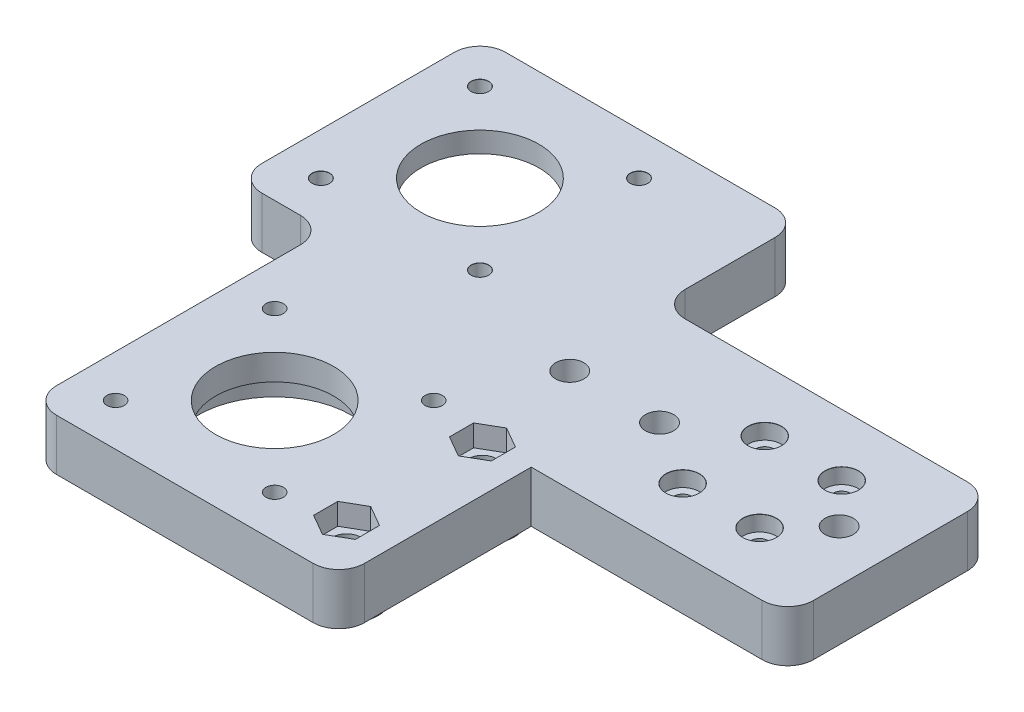
SolidWorks part; units mm, degrees
ref_plane "Front Plane" through (0, 0, 0) normal (0, 0, 1) x (1, 0, 0)
ref_plane "Top Plane" through (0, 0, 0) normal (0, 1, 0) x (1, 0, 0)
ref_plane "Right Plane" through (0, 0, 0) normal (1, 0, 0) x (0, 0, -1)
sketch "Sketch1" plane through (0, 0, 0) normal (0, 1, 0) x (1, 0, 0)
  line L0 (0, 0) -> (110, 0) construction
  line L1 (110, 0) -> (110, 20) construction
  line L2 (110, 20) -> (0, 20) construction
  line L3 (0, 20) -> (0, 0) construction
  line L4 (110, 30) -> (110, -10) construction
  line L5 (110, 30) -> (80, 30) construction
  line L6 (80, 30) -> (80, -10) construction
  line L7 (80, -10) -> (110, -10) construction
  line L8 (0, 67.5) -> (0, -47.5)
  line L16 (0, 67.5) -> (60, 67.5)
  line L18 (0, -47.5) -> (60, -47.5)
  line L19 (60, 67.5) -> (60, 30)
  line L22 (110, -10) -> (60, -10)
  line L23 (60, -10) -> (60, -47.5)
  line L24 (60, 30) -> (110, 30)
  line L25 (110, 30) -> (110, -10)
  point P8 (110, 10)
  point P13 (0, 10)
  dimension "D1" = 20
  dimension "D2" = 37.5
  dimension "D3" = 30
  dimension "D4" = 40
  dimension "D5" = 110
  dimension "D6" = 20
extrude "Boss-Extrude1" add sketch "Sketch1" along normal blind 10
fillet "Fillet1" radius 5 7 edges at (60, 5, -30) (110, 5, -30) (110, 5, 10) (0, 5, 47.5) (0, 5, -67.5) (60, 5, -67.5) (60, 5, 47.5)
sketch "Sketch3" plane through (0, 10, 0) normal (0, 1, 0) x (1, 0, 0)
  line L0 (5, -47.5) -> (55, -47.5) construction
  line L1 (0, 62.5) -> (0, -42.5) construction
  circle A0 centre (23.75, -23.75) radius 11.5
  dimension "D3" = 23
  dimension "D1" = 23.75
  dimension "D2" = 23.75
extrude "Cut-Extrude1" cut sketch "Sketch3" against normal blind 10
sketch "Sketch4" plane through (0, 0, 0) normal (0, -1, 0) x (1, 0, 0)
  line L1 (39.25, 39.25) -> (8.25, 39.25)
  line L2 (39.25, 39.25) -> (39.25, 8.25)
  line L3 (39.25, 8.25) -> (8.25, 8.25)
  line L4 (8.25, 39.25) -> (8.25, 8.25)
  line L5 (39.25, 39.25) -> (8.25, 8.25) construction
  line L6 (39.25, 8.25) -> (8.25, 39.25) construction
  point P0 (23.75, 23.75)
  dimension "D1" = 31
hole_wizard "CBORE for M3 SHCS1" positions "Sketch5" profile "Sketch6" counterbore size "M3" standard "ANSI Metric" end condition through all
sketch "Sketch5" plane through (0, 0, 0) normal (0, -1, 0) x (-1, 0, 0)
  point P0 (-39.25, -8.25)
  point P3 (-8.25, -39.25)
  point P6 (-8.25, -8.25)
  point P9 (-39.25, -39.25)
sketch "Sketch6" plane through (39.25, 0, 8.25) normal (1, 0, 0) x (0, 0, -1)
  line L0 (0, 0) -> (0, 10)
  line L1 (0, 10) -> (1.7, 10)
  line L3 (1.7, 10) -> (1.7, 3)
  line L4 (3.25, 3) -> (1.7, 3)
  line L5 (3.25, 3) -> (3.25, 0.025)
  line L6 (3.25, 0.025) -> (3.275, 0)
  line L7 (3.275, 0) -> (0, 0)
  line L8 (-3.25, 0.025) -> (-3.275, 0) construction
  line L11 (0, -6.35) -> (0, 107.95) construction
  dimension "Thru Hole Dia." = 3.4
  dimension "Thru Hole Depth" = 10
  dimension "C'Bore Dia." = 6.5
  dimension "C'Bore Depth" = 3
  dimension "Near C'Sink Dia." = 6.55
  dimension "Near C'Sink Angle" = 90
sketch "Sketch7" plane through (0, 10, 0) normal (0, 1, 0) x (1, 0, 0)
  line L1 (92.5, 18) -> (77.5, 18)
  line L2 (92.5, 18) -> (92.5, 2)
  line L3 (92.5, 2) -> (77.5, 2)
  line L4 (77.5, 18) -> (77.5, 2)
  line L5 (92.5, 18) -> (77.5, 2) construction
  line L6 (92.5, 2) -> (77.5, 18) construction
  line L7 (110, 10) -> (0, 10)
  line L8 (0, 67.5) -> (0, -47.5) construction
  line L10 (110, 30) -> (110, -10) construction
  point P0 (85, 10)
  dimension "D1" = 15
  dimension "D2" = 16
  dimension "D3" = 25
hole_wizard "CBORE for M3 SHCS2" positions "Sketch8" profile "Sketch9" counterbore size "M3" standard "ANSI Metric" end condition through all
sketch "Sketch8" plane through (0, 10, 0) normal (0, 1, 0) x (1, 0, 0)
  point P0 (77.5, 18)
  point P3 (92.5, 18)
  point P6 (92.5, 2)
  point P9 (77.5, 2)
sketch "Sketch9" plane through (77.5, 10, -18) normal (1, 0, 0) x (0, 0, 1)
  line L0 (0, 0) -> (0, 10)
  line L1 (0, 10) -> (1.7, 10)
  line L3 (1.7, 10) -> (1.7, 3)
  line L4 (3.25, 3) -> (1.7, 3)
  line L5 (3.25, 3) -> (3.25, 0.025)
  line L6 (3.25, 0.025) -> (3.275, 0)
  line L7 (3.275, 0) -> (0, 0)
  line L8 (-3.25, 0.025) -> (-3.275, 0) construction
  line L11 (0, -6.35) -> (0, 107.95) construction
  dimension "Thru Hole Dia." = 3.4
  dimension "Thru Hole Depth" = 10
  dimension "C'Bore Dia." = 6.5
  dimension "C'Bore Depth" = 3
  dimension "Near C'Sink Dia." = 6.55
  dimension "Near C'Sink Angle" = 90
sketch "Sketch10" plane through (0, 0, 0) normal (0, -1, 0) x (1, 0, 0)
  line L0 (110, -10) -> (0, -10) construction
  line L1 (110, 5) -> (110, -25) construction
  line L2 (0, -62.5) -> (0, 42.5) construction
  point P6 (100, -10)
  point P7 (30, -10)
  point P8 (47.5, -10)
  point P9 (65, -10)
  dimension "D1" = 30
  dimension "D2" = 17.5
  dimension "D3" = 17.5
  dimension "D4" = 10
hole_wizard "CBORE for M5 SHCS1" positions "Sketch13" profile "Sketch12" counterbore size "M5" standard "ANSI Metric" end condition through all
sketch "Sketch13" plane through (0, 0, 0) normal (0, -1, 0) x (-1, 0, 0)
  point P0 (-100, 10)
  point P3 (-65, 10)
  point P6 (-47.5, 10)
sketch "Sketch12" plane through (100, 0, -10) normal (1, 0, 0) x (0, 0, -1)
  line L0 (0, 0) -> (0, 10)
  line L1 (0, 10) -> (2.75, 10)
  line L3 (2.75, 10) -> (2.75, 5)
  line L4 (5, 5) -> (2.75, 5)
  line L5 (5, 5) -> (5, 0.025)
  line L6 (5, 0.025) -> (5.025, 0)
  line L7 (5.025, 0) -> (0, 0)
  line L8 (-5, 0.025) -> (-5.025, 0) construction
  line L11 (0, -6.35) -> (0, 107.95) construction
  dimension "Thru Hole Dia." = 5.5
  dimension "Thru Hole Depth" = 10
  dimension "C'Bore Dia." = 10
  dimension "C'Bore Depth" = 5
  dimension "Near C'Sink Dia." = 10.05
  dimension "Near C'Sink Angle" = 90
sketch "Sketch14" plane through (0, 10, 0) normal (0, 1, 0) x (1, 0, 0)
  line L0 (0, 10) -> (-17.5, 10)
  line L1 (0, 62.5) -> (0, -42.5) construction
  line L2 (-17.5, 10) -> (-17.5, 67.5)
  line L3 (-17.5, 67.5) -> (5, 67.5)
  line L4 (0, 62.5) -> (0, 10)
  arc A0 (5, 67.5) -> (0, 62.5) centre (5, 62.5) ccw construction
  arc A1 (5, 67.5) -> (0, 62.5) centre (5, 62.5) ccw
  dimension "D1" = 17.5
extrude "Boss-Extrude2" add sketch "Sketch14" against normal blind 10
sketch "Sketch15" plane through (0, 10, 0) normal (0, 1, 0) x (1, 0, 0)
  line L0 (-17.5, 67.5) -> (55, 67.5)
  line L1 (-17.5, 67.5) -> (-17.5, 57.5)
  line L2 (-17.5, 67.5) -> (-17.5, 10) construction
  line L3 (-17.5, 57.5) -> (60, 57.5)
  line L5 (60, 35) -> (60, 62.5) construction
  line L6 (60, 57.5) -> (60, 62.5)
  arc A2 (60, 62.5) -> (55, 67.5) centre (55, 62.5) ccw construction
  arc A3 (60, 62.5) -> (55, 67.5) centre (55, 62.5) ccw
  dimension "D1" = 10
extrude "Cut-Extrude2" cut sketch "Sketch15" against normal blind 10
fillet "Fillet2" radius 5 4 edges at (0, 5, -10) (60, 5, -57.5) (-17.5, 5, -57.5) (-17.5, 5, -10)
sketch "Sketch16" plane through (0, 10, 0) normal (0, 1, 0) x (1, 0, 0)
  line L0 (-12.5, 57.5) -> (55, 57.5) construction
  line L1 (-17.5, 52.5) -> (-17.5, 15) construction
  circle A0 centre (6.25, 33.75) radius 11.5
  dimension "D1" = 23
  dimension "D2" = 23.75
  dimension "D3" = 23.75
extrude "Cut-Extrude3" cut sketch "Sketch16" against normal through all
sketch "Sketch17" plane through (0, 10, 0) normal (0, 1, 0) x (1, 0, 0)
  line L1 (21.75, 49.25) -> (-9.25, 49.25)
  line L2 (21.75, 49.25) -> (21.75, 18.25)
  line L3 (21.75, 18.25) -> (-9.25, 18.25)
  line L4 (-9.25, 49.25) -> (-9.25, 18.25)
  line L5 (21.75, 49.25) -> (-9.25, 18.25) construction
  line L6 (21.75, 18.25) -> (-9.25, 49.25) construction
  point P0 (6.25, 33.75)
  dimension "D1" = 31
hole_wizard "M3 Clearance Hole1" positions "Sketch18" profile "Sketch19" hole size "M3" standard "ANSI Metric" end condition through all
sketch "Sketch18" plane through (0, 10, 0) normal (0, 1, 0) x (1, 0, 0)
  point P0 (-9.25, 49.25)
  point P3 (21.75, 49.25)
  point P6 (21.75, 18.25)
  point P9 (-9.25, 18.25)
sketch "Sketch19" plane through (-9.25, 10, -49.25) normal (1, 0, 0) x (0, 0, 1)
  line L0 (0, 0) -> (0, 10)
  line L1 (0, 10) -> (1.7, 10)
  line L2 (1.7, 10) -> (1.7, 0.025)
  line L3 (1.7, 0.025) -> (1.725, 0)
  line L5 (1.725, 0) -> (0, 0)
  line L6 (-1.7, 0.025) -> (-1.725, 0) construction
  line L11 (0, -6.35) -> (0, 107.95) construction
  dimension "Thru Hole Dia." = 3.4
  dimension "Thru Hole Depth" = 10
  dimension "Near C'Sink Dia." = 3.45
  dimension "Near C'Sink Angle" = 90
sketch "Sketch20" plane through (0, 10, 0) normal (0, 1, 0) x (1, 0, 0)
  line L0 (23.75, -23.75) -> (60, -23.75) construction
  line L1 (60, -42.5) -> (60, -10) construction
  line L2 (51, -10.51) -> (51, -36.99) construction
  line L4 (55.0703, -8.16) -> (51, -5.81)
  line L5 (51, -5.81) -> (46.9297, -8.16)
  line L6 (46.9297, -8.16) -> (46.9297, -12.86)
  line L7 (46.9297, -12.86) -> (51, -15.21)
  line L8 (51, -15.21) -> (55.0703, -12.86)
  line L9 (55.0703, -12.86) -> (55.0703, -8.16)
  line L10 (51, -32.29) -> (46.9297, -34.64)
  line L11 (46.9297, -34.64) -> (46.9297, -39.34)
  line L12 (46.9297, -39.34) -> (51, -41.69)
  line L13 (51, -41.69) -> (55.0703, -39.34)
  line L14 (55.0703, -39.34) -> (55.0703, -34.64)
  line L15 (55.0703, -34.64) -> (51, -32.29)
  line L18 (0, 5) -> (0, -42.5) construction
  circle A0 centre (51, -10.51) radius 4.0703 construction
  circle A1 centre (51, -36.99) radius 4.0703 construction
  point P8 (51, -23.75)
  point P25 (51, -36.99)
  point P26 (51, -10.51)
  dimension "D1" = 26.48
  dimension "D2" = 9
  dimension "D3" = 4.7
extrude "Cut-Extrude4" cut sketch "Sketch20" against normal blind 4.2
hole_wizard "M5 Clearance Hole1" positions "Sketch22" profile "Sketch23" hole size "M5" standard "ANSI Metric" end condition through all
sketch "Sketch22" plane through (0, 10, 0) normal (0, 1, 0) x (1, 0, 0)
  point P0 (51, -10.51)
  point P3 (51, -36.99)
sketch "Sketch23" plane through (51, 10, 10.51) normal (1, 0, 0) x (0, 0, 1)
  line L0 (0, 0) -> (0, 10)
  line L1 (0, 10) -> (2.75, 10)
  line L2 (2.75, 10) -> (2.75, 0.025)
  line L3 (2.75, 0.025) -> (2.775, 0)
  line L5 (2.775, 0) -> (0, 0)
  line L6 (-2.75, 0.025) -> (-2.775, 0) construction
  line L11 (0, -6.35) -> (0, 107.95) construction
  dimension "Thru Hole Dia." = 5.5
  dimension "Thru Hole Depth" = 10
  dimension "Near C'Sink Dia." = 5.55
  dimension "Near C'Sink Angle" = 90
sketch "Sketch25" plane through (0, 0, 0) normal (0, -1, 0) x (1, 0, 0)
  circle A0 centre (23.75, 23.75) radius 15
  dimension "D1" = 30
extrude "Cut-Extrude6" cut sketch "Sketch25" against normal blind 5
sketch "Sketch26" plane through (0, 0, 0) normal (0, -1, 0) x (1, 0, 0)
  circle A0 centre (51, 36.99) radius 6.25
  circle A1 centre (51, 36.99) radius 2.75 construction
  circle A2 centre (51, 36.99) radius 2.75
  circle A3 centre (51, 10.51) radius 6.25
  circle A4 centre (51, 10.51) radius 2.75 construction
  circle A5 centre (51, 10.51) radius 2.75
  dimension "D1" = 12.5
extrude "Boss-Extrude3" add sketch "Sketch26" along normal blind 2.9
sketch "Sketch27" plane through (0, 10, 0) normal (0, 1, 0) x (1, 0, 0)
  line L0 (65, 30) -> (45, 30)
  line L1 (45, 30) -> (45, 57.5)
  line L2 (-12.5, 57.5) -> (55, 57.5) construction
  line L3 (45, 57.5) -> (55, 57.5)
  line L4 (60, 35) -> (60, 52.5) construction
  line L5 (60, 35) -> (60, 52.5)
  arc A0 (60, 35) -> (65, 30) centre (65, 35) ccw construction
  arc A1 (60, 52.5) -> (55, 57.5) centre (55, 52.5) ccw construction
  arc A2 (60, 35) -> (65, 30) centre (65, 35) ccw
  arc A3 (60, 52.5) -> (55, 57.5) centre (55, 52.5) ccw
  dimension "D1" = 15
extrude "Cut-Extrude7" cut sketch "Sketch27" against normal blind 10
fillet "Fillet3" radius 5 2 edges at (45, 5, -57.5) (45, 5, -30)
sketch "Sketch31" plane through (0, 10, 0) normal (0, 1, 0) x (1, 0, 0)
  line L0 (-10.5429, 54.2071) -> (-14.2071, 50.5429) construction
  line L1 (22.3358, 54.5) -> (-9.8358, 54.5) construction
  line L2 (26.7071, 50.5429) -> (23.0429, 54.2071) construction
  line L3 (27, 17.6642) -> (27, 49.8358) construction
  line L4 (23.0429, 13.2929) -> (26.7071, 16.9571) construction
  line L5 (-9.8358, 13) -> (22.3358, 13) construction
  line L6 (-14.2071, 16.9571) -> (-10.5429, 13.2929) construction
  line L7 (-14.5, 49.8358) -> (-14.5, 17.6642) construction
  line L8 (-10.5429, 54.2071) -> (-14.2071, 50.5429) construction
  line L9 (22.3358, 54.5) -> (-9.8358, 54.5) construction
  line L10 (-14.7, 49.8358) -> (-14.7, 17.6642)
  line L11 (-14.3485, 16.8157) -> (-10.6843, 13.1515)
  line L12 (-9.8358, 12.8) -> (22.3358, 12.8)
  line L13 (23.1843, 13.1515) -> (26.8485, 16.8157)
  line L14 (27.2, 17.6642) -> (27.2, 49.8358)
  line L15 (26.8485, 50.6843) -> (23.1843, 54.3485)
  line L16 (22.3358, 54.7) -> (-9.8358, 54.7)
  line L17 (-10.6843, 54.3485) -> (-14.3485, 50.6843)
  line L30 (26.7071, 50.5429) -> (23.0429, 54.2071) construction
  line L31 (27, 17.6642) -> (27, 49.8358) construction
  line L32 (23.0429, 13.2929) -> (26.7071, 16.9571) construction
  line L33 (-9.8358, 13) -> (22.3358, 13) construction
  line L34 (-14.2071, 16.9571) -> (-10.5429, 13.2929) construction
  line L35 (-14.5, 49.8358) -> (-14.5, 17.6642) construction
  arc A0 (-14.2071, 50.5429) -> (-14.5, 49.8358) centre (-13.5, 49.8358) ccw construction
  arc A1 (-9.8358, 54.5) -> (-10.5429, 54.2071) centre (-9.8358, 53.5) ccw construction
  arc A2 (23.0429, 54.2071) -> (22.3358, 54.5) centre (22.3358, 53.5) ccw construction
  arc A3 (27, 49.8358) -> (26.7071, 50.5429) centre (26, 49.8358) ccw construction
  arc A4 (26.7071, 16.9571) -> (27, 17.6642) centre (26, 17.6642) ccw construction
  arc A5 (22.3358, 13) -> (23.0429, 13.2929) centre (22.3358, 14) ccw construction
  arc A6 (-10.5429, 13.2929) -> (-9.8358, 13) centre (-9.8358, 14) ccw construction
  arc A7 (-14.5, 17.6642) -> (-14.2071, 16.9571) centre (-13.5, 17.6642) ccw construction
  arc A8 (-14.2071, 50.5429) -> (-14.5, 49.8358) centre (-13.5, 49.8358) ccw construction
  arc A9 (-14.3485, 50.6843) -> (-14.7, 49.8358) centre (-13.5, 49.8358) ccw
  arc A10 (-14.7, 17.6642) -> (-14.3485, 16.8157) centre (-13.5, 17.6642) ccw
  arc A11 (-10.6843, 13.1515) -> (-9.8358, 12.8) centre (-9.8358, 14) ccw
  arc A12 (22.3358, 12.8) -> (23.1843, 13.1515) centre (22.3358, 14) ccw
  arc A14 (26.8485, 16.8157) -> (27.2, 17.6642) centre (26, 17.6642) ccw
  arc A15 (27.2, 49.8358) -> (26.8485, 50.6843) centre (26, 49.8358) ccw
  arc A17 (23.1843, 54.3485) -> (22.3358, 54.7) centre (22.3358, 53.5) ccw
  arc A27 (-9.8358, 54.5) -> (-10.5429, 54.2071) centre (-9.8358, 53.5) ccw construction
  arc A28 (23.0429, 54.2071) -> (22.3358, 54.5) centre (22.3358, 53.5) ccw construction
  arc A29 (27, 49.8358) -> (26.7071, 50.5429) centre (26, 49.8358) ccw construction
  arc A30 (26.7071, 16.9571) -> (27, 17.6642) centre (26, 17.6642) ccw construction
  arc A31 (22.3358, 13) -> (23.0429, 13.2929) centre (22.3358, 14) ccw construction
  arc A32 (-10.5429, 13.2929) -> (-9.8358, 13) centre (-9.8358, 14) ccw construction
  arc A33 (-14.5, 17.6642) -> (-14.2071, 16.9571) centre (-13.5, 17.6642) ccw construction
  arc A34 (-9.8358, 54.7) -> (-10.6843, 54.3485) centre (-9.8358, 53.5) ccw
  dimension "D1" = 0.2
extrude "Cut-Extrude9" cut sketch "Sketch31" along normal blind 6 from surface starting at face at (51, 0, 43.24)
